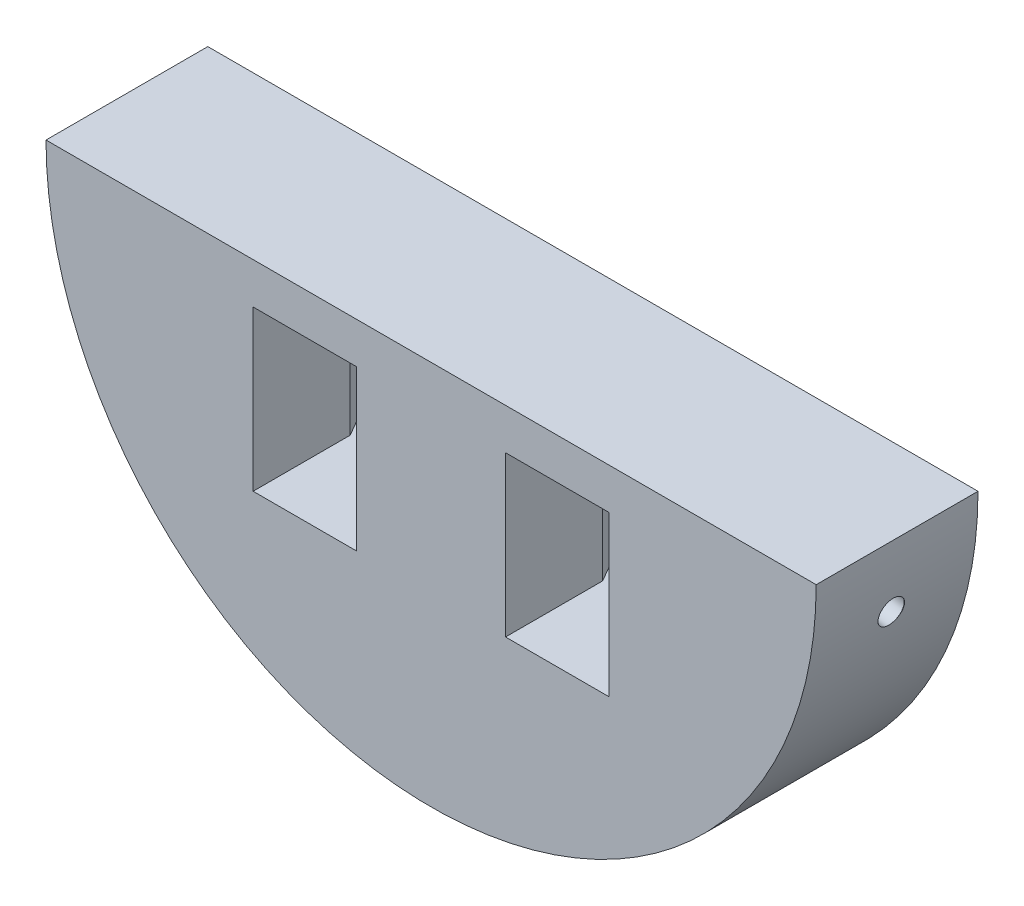
SolidWorks part; units mm, degrees
ref_plane "Front Plane" through (0, 0, 0) normal (0, 0, 1) x (1, 0, 0)
ref_plane "Top Plane" through (0, 0, 0) normal (0, 1, 0) x (1, 0, 0)
ref_plane "Right Plane" through (0, 0, 0) normal (1, 0, 0) x (0, 0, -1)
sketch "Sketch1" plane through (0, 0, 0) normal (0, 0, 1) x (1, 0, 0)
  line L0 (-119, 0) -> (0, 0)
  line L3 (-48, -31) -> (-32, -31)
  line L4 (-48, -31) -> (-48, -15)
  line L5 (-48, -15) -> (-32, -15)
  line L6 (-32, -31) -> (-32, -15)
  line L7 (-87, -31) -> (-71, -31)
  line L8 (-87, -31) -> (-87, -15)
  line L9 (-87, -15) -> (-71, -15)
  line L10 (-71, -31) -> (-71, -15)
  arc A1 (-119, 0) -> (0, 0) centre (-59.5, 0) ccw
  point P0 (-79, -15)
  point P13 (-40, -15)
  dimension "D1" = 19.5
  dimension "D7" = 59.5
  dimension "D2" = 15
  dimension "D4" = 16
  dimension "D5" = 19.5
extrude "Boss-Extrude1" add sketch "Sketch1" along normal blind 25
hole_wizard "Ø4.0mm Dowel Hole2" positions "3DSketch2" profile "Sketch4" hole size "Ø4.0" standard "ANSI Metric"
sketch3d "3DSketch2"
  line L2 (0, 0, 25) -> (0, 0, 0) construction
  line L4 (0, 0, 25) -> (0, 0, 0) construction
  line L5 (0, 0, 12.5) -> (-0.9039, -10.3321, 12.5) construction
  line L8 (-59.5, 0, 0) -> (-59.5, 0, 25) construction
  line L9 (0, 0, 0) -> (-119, 0, 0) construction
  line L10 (0, 0, 25) -> (-119, 0, 25) construction
  line L12 (-59.5, 0, 12.5) -> (-0.9039, -10.3321, 12.5) construction
  line L16 (-59.5, 0, 12.5) -> (0, 0, 12.5) construction
  point P0 (-0.9039, -10.3321, 12.5)
  point P16 (-0.9039, -10.3321, 12.5)
  point P23 (-0.9039, -10.3321, 12.5)
  point P25 (-0.9039, -10.3321, 12.5)
  dimension "D1" = 10
sketch "Sketch4" plane through (-0.9039, -10.3321, 12.5) normal (0, 0, 1) x (0.1736, 0.9848, 0)
  line L0 (0, 0) -> (0, 11.2017)
  line L1 (0, 11.2017) -> (2, 10)
  line L2 (2, 10) -> (2, 0.025)
  line L3 (2, 0.025) -> (2.025, 0)
  line L5 (2.025, 0) -> (0, 0)
  line L6 (-2, 0.025) -> (-2.025, 0) construction
  line L10 (0, 11.2017) -> (-2, 10) construction
  line L11 (0, -6.35) -> (0, 107.95) construction
  dimension "Hole Dia." = 4
  dimension "Hole Depth" = 10
  dimension "Near C'Sink Dia." = 4.05
  dimension "Near C'Sink Angle" = 90
  dimension "Drill Angle" = 118
pattern_circular "CirPattern1" count 5 over 160 about axis through (-59.5, 0, 0) along (0, 0, 1) of "Ø4.0mm Dowel Hole2" reverse direction yes
chamfer "Chamfer1" distance 15 angle 30 2 edges at (-79, -15, 25) (-40, -15, 25) first distance on face at (-79, -15, 12.5) first distance on face at (-40, -15, 12.5)
chamfer "Chamfer2" distance 10 angle 30 6 edges at (-48, -23, 0) (-40, -15, 0) (-32, -23, 0) (-87, -23, 0) (-79, -15, 0) (-71, -23, 0) first distance on face at (-48, -19.6679, 12) first distance on face at (-40, -15, 5) first distance on face at (-32, -19.6679, 12) first distance on face at (-87, -19.6679, 12) first distance on face at (-79, -15, 5) first distance on face at (-71, -19.6679, 12)
